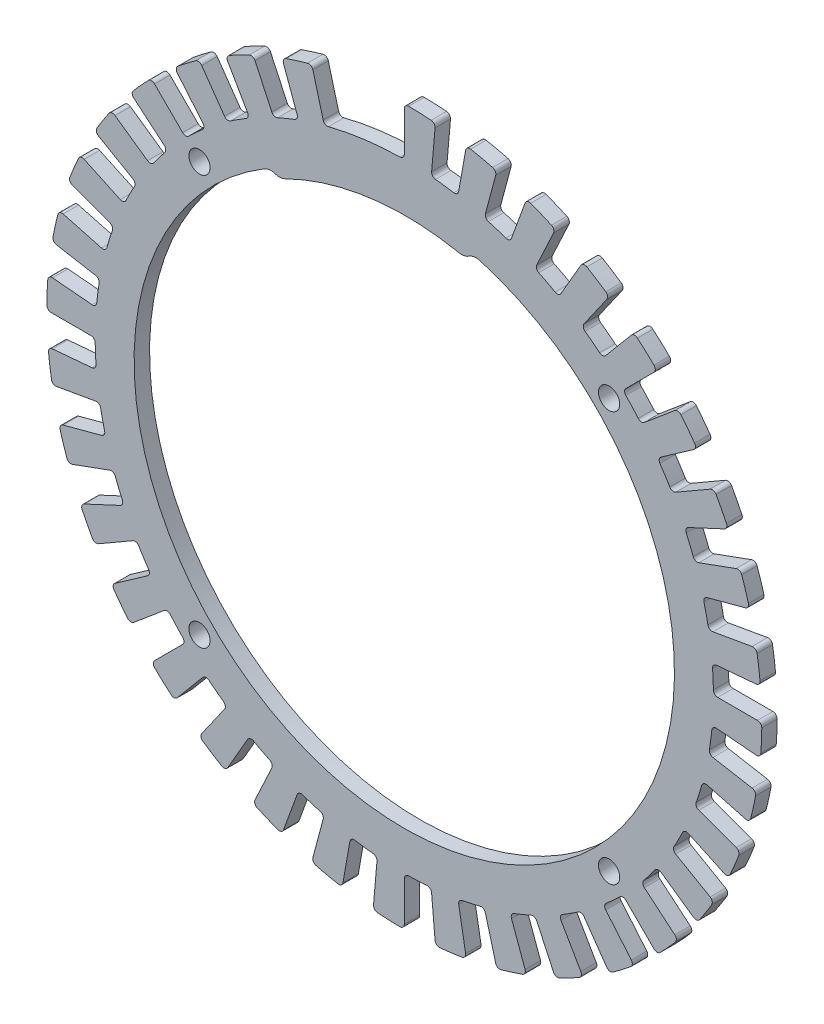
SolidWorks part; units mm, degrees
ref_plane "Front Plane" through (0, 0, 0) normal (0, 0, 1) x (1, 0, 0)
ref_plane "Top Plane" through (0, 0, 0) normal (0, 1, 0) x (1, 0, 0)
ref_plane "Right Plane" through (0, 0, 0) normal (1, 0, 0) x (0, 0, -1)
sketch "Sketch1" plane through (0, 0, 0) normal (0, 0, 1) x (1, 0, 0)
  line L0 (0, 82.7) -> (0, 71.5) construction
  line L1 (7.2078, 82.3853) -> (6.2316, 71.2279) construction
  line L2 (0, 71.5) -> (0, 0) construction
  line L3 (6.2316, 71.2279) -> (0, 0) construction
  line L4 (12.5883, 71.3918) -> (14.186, 80.4528) construction
  line L5 (12.5883, 71.3918) -> (0, 0) construction
  line L8 (0, 0) -> (47.3762, 47.3762) construction
  line L12 (50.5581, 50.5581) -> (47.3762, 47.3762) construction
  line L15 (47.3762, 47.3762) -> (44.1942, 44.1942) construction
  line L18 (7.3144, 72.1301) -> (6.3182, 72.2172) construction
  line L21 (7.3144, 72.1301) -> (7.2135, 71.1352) construction
  line L24 (12.5883, 71.3918) -> (11.6035, 71.5654) construction
  line L27 (11.6035, 71.5654) -> (11.4434, 70.5783) construction
  line L30 (1.0122, 82.6938) -> (1, 81.6939) construction
  line L33 (1, 81.6939) -> (0, 81.6939) construction
  line L36 (7.1201, 81.383) -> (6.1239, 81.4702) construction
  line L39 (6.1239, 81.4702) -> (6.1989, 82.4674) construction
  line L42 (7.1201, 81.383) -> (6.3182, 72.2172)
  line L45 (0, 81.6939) -> (0, 72.4931)
  line L48 (0, 72.4931) -> (-1, 72.4931) construction
  line L51 (-1, 72.4931) -> (-0.9862, 71.4932) construction
  line L109 (0, -82.7) -> (0, -71.5) [skipped]
  line L111 (14.3607, 81.4436) -> (12.4158, 70.4138) [skipped]
  line L115 (41.35, 71.6203) -> (35.75, 61.9208) [skipped]
  line L117 (53.1585, 63.3519) -> (45.9593, 54.7722) [skipped]
  line L118 (-63.3519, -53.1585) -> (-54.7722, -45.9593) [skipped]
  line L119 (63.3519, 53.1585) -> (54.7722, 45.9593) [skipped]
  line L121 (71.6203, 41.35) -> (61.9208, 35.75) [skipped]
  line L123 (77.7126, 28.2851) -> (67.188, 24.4544) [skipped]
  line L125 (81.4436, 14.3607) -> (70.4138, 12.4158) [skipped]
  line L127 (82.7, 0) -> (71.5, 0) [skipped]
  line L129 (81.4436, -14.3607) -> (70.4138, -12.4158) [skipped]
  line L131 (77.7126, -28.2851) -> (67.188, -24.4544) [skipped]
  line L133 (71.6203, -41.35) -> (61.9208, -35.75) [skipped]
  line L135 (63.3519, -53.1585) -> (54.7722, -45.9593) [skipped]
  line L137 (53.1585, -63.3519) -> (45.9593, -54.7722) [skipped]
  line L139 (41.35, -71.6203) -> (35.75, -61.9208) [skipped]
  line L141 (28.2851, -77.7126) -> (24.4544, -67.188) [skipped]
  line L142 (14.3607, -81.4436) -> (12.4158, -70.4138) [skipped]
  line L143 (34.9505, 74.9517) -> (30.2172, 64.801) [skipped]
  line L144 (47.4348, 67.7439) -> (41.0107, 58.5694) [skipped]
  line L145 (58.4777, 58.4777) -> (50.5581, 50.5581) [skipped]
  line L146 (67.7439, 47.4348) -> (58.5694, 41.0107) [skipped]
  line L147 (74.9517, 34.9505) -> (64.801, 30.2172) [skipped]
  line L148 (79.8821, 21.4043) -> (69.0637, 18.5056) [skipped]
  line L149 (82.3853, 7.2078) -> (71.2279, 6.2316) [skipped]
  line L150 (82.3853, -7.2078) -> (71.2279, -6.2316) [skipped]
  line L151 (79.8821, -21.4043) -> (69.0637, -18.5056) [skipped]
  line L152 (74.9517, -34.9505) -> (64.801, -30.2172) [skipped]
  line L153 (67.7439, -47.4348) -> (58.5694, -41.0107) [skipped]
  line L154 (58.4777, -58.4777) -> (50.5581, -50.5581) [skipped]
  line L155 (47.4348, -67.7439) -> (41.0107, -58.5694) [skipped]
  line L156 (34.9505, -74.9517) -> (30.2172, -64.801) [skipped]
  line L157 (21.4043, -79.8821) -> (18.5056, -69.0637) [skipped]
  line L158 (7.2078, -82.3853) -> (6.2316, -71.2279) [skipped]
  line L159 (-7.2078, -82.3853) -> (-6.2316, -71.2279) [skipped]
  line L160 (-21.4043, -79.8821) -> (-18.5056, -69.0637) [skipped]
  line L161 (-34.9505, -74.9517) -> (-30.2172, -64.801) [skipped]
  line L162 (-47.4348, -67.7439) -> (-41.0107, -58.5694) [skipped]
  line L163 (-58.4777, -58.4777) -> (-50.5581, -50.5581) [skipped]
  line L164 (-67.7439, -47.4348) -> (-58.5694, -41.0107) [skipped]
  line L165 (-74.9517, -34.9505) -> (-64.801, -30.2172) [skipped]
  line L166 (-79.8821, -21.4043) -> (-69.0637, -18.5056) [skipped]
  line L167 (-82.3853, -7.2078) -> (-71.2279, -6.2316) [skipped]
  line L168 (-82.3853, 7.2078) -> (-71.2279, 6.2316) [skipped]
  line L169 (-79.8821, 21.4043) -> (-69.0637, 18.5056) [skipped]
  line L170 (-74.9517, 34.9505) -> (-64.801, 30.2172) [skipped]
  line L171 (-67.7439, 47.4348) -> (-58.5694, 41.0107) [skipped]
  line L172 (-58.4777, 58.4777) -> (-50.5581, 50.5581) [skipped]
  line L173 (-47.4348, 67.7439) -> (-41.0107, 58.5694) [skipped]
  line L174 (-34.9505, 74.9517) -> (-30.2172, 64.801) [skipped]
  line L175 (-21.4043, 79.8821) -> (-18.5056, 69.0637) [skipped]
  line L176 (21.4043, 79.8821) -> (18.5056, 69.0637) [skipped]
  line L209 (0, 0) -> (-47.3762, -47.3762) construction
  line L210 (0, 0) -> (-47.3762, 47.3762) construction
  line L211 (0, 0) -> (47.3762, -47.3762) construction
  line L212 (14.186, 80.4528) -> (12.5883, 71.3918)
  line L213 (21.1439, 78.9102) -> (18.7626, 70.023)
  line L214 (27.941, 76.7671) -> (24.7941, 68.1212)
  line L215 (34.5253, 74.0398) -> (30.6369, 65.7011)
  line L216 (40.8469, 70.749) -> (36.2466, 62.7809)
  line L217 (46.8577, 66.9197) -> (41.5803, 59.3829)
  line L218 (52.5118, 62.5811) -> (46.5977, 55.5329)
  line L219 (57.7663, 57.7663) -> (51.2604, 51.2604)
  line L220 (62.5811, 52.5118) -> (55.5329, 46.5977)
  line L221 (66.9197, 46.8577) -> (59.3829, 41.5803)
  line L222 (70.749, 40.8469) -> (62.7809, 36.2466)
  line L223 (74.0398, 34.5253) -> (65.7011, 30.6369)
  line L224 (76.7671, 27.941) -> (68.1212, 24.7941)
  line L225 (78.9102, 21.1439) -> (70.023, 18.7626)
  line L226 (80.4528, 14.186) -> (71.3918, 12.5883)
  line L227 (81.383, 7.1201) -> (72.2172, 6.3182)
  line L228 (81.6939, 0) -> (72.4931, 0)
  line L229 (81.383, -7.1201) -> (72.2172, -6.3182)
  line L230 (80.4528, -14.186) -> (71.3918, -12.5883)
  line L231 (78.9102, -21.1439) -> (70.023, -18.7626)
  line L232 (76.7671, -27.941) -> (68.1212, -24.7941)
  line L233 (74.0398, -34.5253) -> (65.7011, -30.6369)
  line L234 (70.749, -40.8469) -> (62.7809, -36.2466)
  line L235 (66.9197, -46.8577) -> (59.3829, -41.5803)
  line L236 (62.5811, -52.5118) -> (55.5329, -46.5977)
  line L237 (57.7663, -57.7663) -> (51.2604, -51.2604)
  line L238 (52.5118, -62.5811) -> (46.5977, -55.5329)
  line L239 (46.8577, -66.9197) -> (41.5803, -59.3829)
  line L240 (40.8469, -70.749) -> (36.2466, -62.7809)
  line L241 (34.5253, -74.0398) -> (30.6369, -65.7011)
  line L242 (27.941, -76.7671) -> (24.7941, -68.1212)
  line L243 (21.1439, -78.9102) -> (18.7626, -70.023)
  line L244 (14.186, -80.4528) -> (12.5883, -71.3918)
  line L245 (7.1201, -81.383) -> (6.3182, -72.2172)
  line L246 (0, -81.6939) -> (0, -72.4931)
  line L247 (-7.1201, -81.383) -> (-6.3182, -72.2172)
  line L248 (-14.186, -80.4528) -> (-12.5883, -71.3918)
  line L249 (-21.1439, -78.9102) -> (-18.7626, -70.023)
  line L250 (-27.941, -76.7671) -> (-24.7941, -68.1212)
  line L251 (-34.5253, -74.0398) -> (-30.6369, -65.7011)
  line L252 (-40.8469, -70.749) -> (-36.2466, -62.7809)
  line L253 (-46.8577, -66.9197) -> (-41.5803, -59.3829)
  line L254 (-52.5118, -62.5811) -> (-46.5977, -55.5329)
  line L255 (-57.7663, -57.7663) -> (-51.2604, -51.2604)
  line L256 (-62.5811, -52.5118) -> (-55.5329, -46.5977)
  line L257 (-66.9197, -46.8577) -> (-59.3829, -41.5803)
  line L258 (-70.749, -40.8469) -> (-62.7809, -36.2466)
  line L259 (-74.0398, -34.5253) -> (-65.7011, -30.6369)
  line L260 (-76.7671, -27.941) -> (-68.1212, -24.7941)
  line L261 (-78.9102, -21.1439) -> (-70.023, -18.7626)
  line L262 (-80.4528, -14.186) -> (-71.3918, -12.5883)
  line L263 (-81.383, -7.1201) -> (-72.2172, -6.3182)
  line L264 (-81.6939, 0) -> (-72.4931, 0)
  line L265 (-81.383, 7.1201) -> (-72.2172, 6.3182)
  line L266 (-80.4528, 14.186) -> (-71.3918, 12.5883)
  line L267 (-78.9102, 21.1439) -> (-70.023, 18.7626)
  line L268 (-76.7671, 27.941) -> (-68.1212, 24.7941)
  line L269 (-74.0398, 34.5253) -> (-65.7011, 30.6369)
  line L270 (-70.749, 40.8469) -> (-62.7809, 36.2466)
  line L271 (-66.9197, 46.8577) -> (-59.3829, 41.5803)
  line L272 (-62.5811, 52.5118) -> (-55.5329, 46.5977)
  line L273 (-57.7663, 57.7663) -> (-51.2604, 51.2604)
  line L274 (-52.5118, 62.5811) -> (-46.5977, 55.5329)
  line L275 (-46.8577, 66.9197) -> (-41.5803, 59.3829)
  line L276 (-40.8469, 70.749) -> (-36.2466, 62.7809)
  line L277 (-34.5253, 74.0398) -> (-30.6369, 65.7011)
  line L278 (-27.941, 76.7671) -> (-24.7941, 68.1212)
  line L279 (-21.1439, 78.9102) -> (-18.7626, 70.023)
  line L280 (-0.9864, 71.4932) -> (-0.9862, 71.4932)
  line L281 (-32.3995, 53.4464) -> (-30.8444, 50.881) construction
  line L282 (-30.8444, 50.881) -> (-29.8635, 53.7161) construction
  line L283 (-29.8635, 53.7161) -> (-28.8826, 56.5512) construction
  line L284 (-28.8826, 56.5512) -> (-27.5181, 53.8795) construction
  line L285 (17.4626, 60.0109) -> (16.6244, 57.1304) construction
  line L286 (16.6244, 57.1304) -> (14.9432, 59.615) construction
  line L289 (13.262, 62.0997) -> (14.9432, 59.615) construction
  line L290 (-7.4414, 56.5227) -> (0, 0) construction
  line L291 (-27.5181, 53.8795) -> (-7.4414, 56.5227) construction
  line L292 (-7.4414, 56.5227) -> (12.6354, 59.1658) construction
  line L293 (13.262, 62.0997) -> (12.6354, 59.1658) construction
  line L294 (-28.4278, 55.6607) -> (13.0531, 61.1217) construction
  circle A0 centre (0, 0) radius 82.7 construction
  arc A1 (-32.3995, 53.4464) -> (17.4626, 60.0109) centre (0, 0) ccw
  circle A73 centre (47.3762, 47.3762) radius 2.4585
  circle A74 centre (47.3762, 47.3762) radius 2.987 construction
  arc A78 (0, 71.5) -> (6.2316, 71.2279) centre (0, 0) cw construction
  arc A79 (6.3182, 72.2172) -> (7.2135, 71.1352) centre (7.3144, 72.1301) ccw
  arc A80 (11.4434, 70.5783) -> (12.5883, 71.3918) centre (11.6035, 71.5654) ccw construction
  arc A81 (7.1201, 81.383) -> (6.1989, 82.4674) centre (6.1239, 81.4702) ccw
  arc A82 (0, 81.6939) -> (1.0122, 82.6938) centre (1, 81.6939) cw
  arc A83 (6.5367, 74.7146) -> (13.0236, 73.8606) centre (0, 0) cw [skipped]
  arc A84 (7.2135, 71.1352) -> (11.4434, 70.5783) centre (0, 0) cw
  arc A85 (0, 82.7) -> (7.2078, 82.3853) centre (0, 0) cw [skipped]
  arc A86 (1.0122, 82.6938) -> (6.1989, 82.4674) centre (0, 0) cw
  arc A87 (28.2851, 77.7126) -> (34.9505, 74.9517) centre (0, 0) cw [skipped]
  arc A88 (31.6964, 67.9731) -> (37.5, 64.9519) centre (0, 0) cw [skipped]
  arc A89 (41.35, 71.6203) -> (47.4348, 67.7439) centre (0, 0) cw [skipped]
  arc A90 (43.0182, 61.4364) -> (48.2091, 57.4533) centre (0, 0) cw [skipped]
  arc A91 (53.1585, 63.3519) -> (58.4777, 58.4777) centre (0, 0) cw [skipped]
  arc A92 (53.033, 53.033) -> (57.4533, 48.2091) centre (0, 0) cw [skipped]
  arc A93 (63.3519, 53.1585) -> (67.7439, 47.4348) centre (0, 0) cw [skipped]
  arc A94 (61.4364, 43.0182) -> (64.9519, 37.5) centre (0, 0) cw [skipped]
  arc A95 (71.6203, 41.35) -> (74.9517, 34.9505) centre (0, 0) cw [skipped]
  arc A96 (67.9731, 31.6964) -> (70.4769, 25.6515) centre (0, 0) cw [skipped]
  arc A97 (77.7126, 28.2851) -> (79.8821, 21.4043) centre (0, 0) cw [skipped]
  arc A98 (72.4444, 19.4114) -> (73.8606, 13.0236) centre (0, 0) cw [skipped]
  arc A99 (81.4436, 14.3607) -> (82.3853, 7.2078) centre (0, 0) cw [skipped]
  arc A100 (74.7146, 6.5367) -> (75, 0) centre (0, 0) cw [skipped]
  arc A101 (82.7, 0) -> (82.3853, -7.2078) centre (0, 0) cw [skipped]
  arc A102 (74.7146, -6.5367) -> (73.8606, -13.0236) centre (0, 0) cw [skipped]
  arc A103 (81.4436, -14.3607) -> (79.8821, -21.4043) centre (0, 0) cw [skipped]
  arc A104 (72.4444, -19.4114) -> (70.4769, -25.6515) centre (0, 0) cw [skipped]
  arc A105 (77.7126, -28.2851) -> (74.9517, -34.9505) centre (0, 0) cw [skipped]
  arc A106 (67.9731, -31.6964) -> (64.9519, -37.5) centre (0, 0) cw [skipped]
  arc A107 (71.6203, -41.35) -> (67.7439, -47.4348) centre (0, 0) cw [skipped]
  arc A108 (61.4364, -43.0182) -> (57.4533, -48.2091) centre (0, 0) cw [skipped]
  arc A109 (63.3519, -53.1585) -> (58.4777, -58.4777) centre (0, 0) cw [skipped]
  arc A110 (53.033, -53.033) -> (48.2091, -57.4533) centre (0, 0) cw [skipped]
  arc A111 (53.1585, -63.3519) -> (47.4348, -67.7439) centre (0, 0) cw [skipped]
  arc A112 (43.0182, -61.4364) -> (37.5, -64.9519) centre (0, 0) cw [skipped]
  arc A113 (41.35, -71.6203) -> (34.9505, -74.9517) centre (0, 0) cw [skipped]
  arc A114 (31.6964, -67.9731) -> (25.6515, -70.4769) centre (0, 0) cw [skipped]
  arc A115 (28.2851, -77.7126) -> (21.4043, -79.8821) centre (0, 0) cw [skipped]
  arc A116 (19.4114, -72.4444) -> (13.0236, -73.8606) centre (0, 0) cw [skipped]
  arc A117 (14.3607, -81.4436) -> (7.2078, -82.3853) centre (0, 0) cw [skipped]
  arc A118 (6.5367, -74.7146) -> (0, -75) centre (0, 0) cw [skipped]
  arc A119 (0, -82.7) -> (-7.2078, -82.3853) centre (0, 0) cw [skipped]
  arc A120 (-6.5367, -74.7146) -> (-13.0236, -73.8606) centre (0, 0) cw [skipped]
  arc A121 (-14.3607, -81.4436) -> (-21.4043, -79.8821) centre (0, 0) cw [skipped]
  arc A122 (-28.2851, -77.7126) -> (-34.9505, -74.9517) centre (0, 0) cw [skipped]
  arc A123 (-19.4114, -72.4444) -> (-25.6515, -70.4769) centre (0, 0) cw [skipped]
  arc A124 (-31.6964, -67.9731) -> (-37.5, -64.9519) centre (0, 0) cw [skipped]
  arc A125 (-41.35, -71.6203) -> (-47.4348, -67.7439) centre (0, 0) cw [skipped]
  arc A126 (-43.0182, -61.4364) -> (-48.2091, -57.4533) centre (0, 0) cw [skipped]
  arc A127 (-53.1585, -63.3519) -> (-58.4777, -58.4777) centre (0, 0) cw [skipped]
  arc A128 (-53.033, -53.033) -> (-57.4533, -48.2091) centre (0, 0) cw [skipped]
  arc A129 (-63.3519, -53.1585) -> (-67.7439, -47.4348) centre (0, 0) cw [skipped]
  arc A130 (-61.4364, -43.0182) -> (-64.9519, -37.5) centre (0, 0) cw [skipped]
  arc A131 (-71.6203, -41.35) -> (-74.9517, -34.9505) centre (0, 0) cw [skipped]
  arc A132 (-67.9731, -31.6964) -> (-70.4769, -25.6515) centre (0, 0) cw [skipped]
  arc A133 (-77.7126, -28.2851) -> (-79.8821, -21.4043) centre (0, 0) cw [skipped]
  arc A134 (-72.4444, -19.4114) -> (-73.8606, -13.0236) centre (0, 0) cw [skipped]
  arc A135 (-81.4436, -14.3607) -> (-82.3853, -7.2078) centre (0, 0) cw [skipped]
  arc A136 (-74.7146, -6.5367) -> (-75, 0) centre (0, 0) cw [skipped]
  arc A137 (-82.7, 0) -> (-82.3853, 7.2078) centre (0, 0) cw [skipped]
  arc A138 (-74.7146, 6.5367) -> (-73.8606, 13.0236) centre (0, 0) cw [skipped]
  arc A139 (-81.4436, 14.3607) -> (-79.8821, 21.4043) centre (0, 0) cw [skipped]
  arc A140 (-72.4444, 19.4114) -> (-70.4769, 25.6515) centre (0, 0) cw [skipped]
  arc A141 (-77.7126, 28.2851) -> (-74.9517, 34.9505) centre (0, 0) cw [skipped]
  arc A142 (-67.9731, 31.6964) -> (-64.9519, 37.5) centre (0, 0) cw [skipped]
  arc A143 (-71.6203, 41.35) -> (-67.7439, 47.4348) centre (0, 0) cw [skipped]
  arc A144 (-61.4364, 43.0182) -> (-57.4533, 48.2091) centre (0, 0) cw [skipped]
  arc A145 (-63.3519, 53.1585) -> (-58.4777, 58.4777) centre (0, 0) cw [skipped]
  arc A146 (-53.033, 53.033) -> (-48.2091, 57.4533) centre (0, 0) cw [skipped]
  arc A147 (-53.1585, 63.3519) -> (-47.4348, 67.7439) centre (0, 0) cw [skipped]
  arc A148 (-43.0182, 61.4364) -> (-37.5, 64.9519) centre (0, 0) cw [skipped]
  arc A149 (-41.35, 71.6203) -> (-34.9505, 74.9517) centre (0, 0) cw [skipped]
  arc A150 (-31.6964, 67.9731) -> (-25.6515, 70.4769) centre (0, 0) cw [skipped]
  arc A151 (-28.2851, 77.7126) -> (-21.4043, 79.8821) centre (0, 0) cw [skipped]
  arc A152 (-19.4114, 72.4444) -> (-13.0236, 73.8606) centre (0, 0) cw [skipped]
  arc A153 (14.3607, 81.4436) -> (21.4043, 79.8821) centre (0, 0) cw [skipped]
  arc A154 (19.4114, 72.4444) -> (25.6515, 70.4769) centre (0, 0) cw [skipped]
  arc A155 (0, 72.4931) -> (-0.9862, 71.4932) centre (-1, 72.4931) cw
  circle A367 centre (-47.3762, -47.3762) radius 2.4585
  circle A368 centre (47.3762, -47.3762) radius 2.4585
  circle A369 centre (-47.3762, 47.3762) radius 2.4585
  circle A370 centre (0, 0) radius 71.5 construction
  arc A371 (12.5883, 71.3918) -> (11.4434, 70.5783) centre (11.6035, 71.5654) cw
  arc A372 (14.186, 80.4528) -> (15.3565, 81.2617) centre (15.1708, 80.2791) cw
  arc A373 (15.3565, 81.2617) -> (20.425, 80.1381) centre (0, 0) cw
  arc A374 (21.1439, 78.9102) -> (20.425, 80.1381) centre (20.178, 79.169) ccw
  arc A375 (18.7626, 70.023) -> (19.4564, 68.8019) centre (19.7285, 69.7641) ccw
  arc A376 (19.4564, 68.8019) -> (23.5254, 67.5189) centre (0, 0) cw
  arc A377 (24.7941, 68.1212) -> (23.5254, 67.5189) centre (23.8544, 68.4633) cw
  arc A378 (27.941, 76.7671) -> (29.2341, 77.3606) centre (28.8806, 76.4251) cw
  arc A379 (29.2341, 77.3606) -> (34.0305, 75.3738) centre (0, 0) cw
  arc A380 (34.5253, 74.0398) -> (34.0305, 75.3738) centre (33.619, 74.4624) ccw
  arc A381 (30.6369, 65.7011) -> (31.1081, 64.3781) centre (31.5432, 65.2784) ccw
  arc A382 (31.1081, 64.3781) -> (34.8925, 62.408) centre (0, 0) cw
  arc A384 (36.2466, 62.7809) -> (34.8925, 62.408) centre (35.3805, 63.2809) cw
  arc A385 (40.8469, 70.749) -> (42.2235, 71.1088) centre (41.713, 70.249) cw
  arc A386 (42.2235, 71.1088) -> (46.602, 68.3194) centre (0, 0) cw
  arc A387 (46.8577, 66.9197) -> (46.602, 68.3194) centre (46.0385, 67.4933) ccw
  arc A388 (41.5803, 59.3829) -> (41.8147, 57.9981) centre (42.3995, 58.8093) ccw
  arc A389 (41.8147, 57.9981) -> (45.1995, 55.4009) centre (0, 0) cw
  arc A390 (46.5977, 55.5329) -> (45.1995, 55.4009) centre (45.8316, 56.1757) cw
  arc A391 (52.5118, 62.5811) -> (53.93, 62.6965) centre (53.2779, 61.9384) cw
  arc A392 (53.93, 62.6965) -> (57.7576, 59.1891) centre (0, 0) cw
  arc A393 (57.7663, 57.7663) -> (57.7576, 59.1891) centre (57.0592, 58.4734) ccw
  arc A394 (51.2604, 51.2604) -> (51.2507, 49.856) centre (51.9675, 50.5533) ccw
  arc A395 (51.2507, 49.856) -> (54.133, 46.7104) centre (0, 0) cw
  arc A396 (55.5329, 46.5977) -> (54.133, 46.7104) centre (54.8902, 47.3637) cw
  arc A397 (62.5811, 52.5118) -> (63.9978, 52.3791) centre (63.2239, 51.7458) cw
  arc A398 (63.9978, 52.3791) -> (67.1582, 48.2604) centre (0, 0) cw
  arc A399 (66.9197, 46.8577) -> (67.1582, 48.2604) centre (66.3461, 47.6768) ccw
  arc A400 (59.3829, 41.5803) -> (59.1295, 40.199) centre (59.9565, 40.7612) ccw
  arc A401 (59.1295, 40.199) -> (61.4218, 36.6007) centre (0, 0) cw
  arc A402 (62.7809, 36.2466) -> (61.4218, 36.6007) centre (62.2809, 37.1126) cw
  arc A403 (70.749, 40.8469) -> (72.1211, 40.4703) centre (71.249, 39.9809) cw
  arc A404 (72.1211, 40.4703) -> (74.5182, 35.8653) centre (0, 0) cw
  arc A405 (74.0398, 34.5253) -> (74.5182, 35.8653) centre (73.6172, 35.4316) ccw
  arc A406 (65.7011, 30.6369) -> (65.2116, 29.3205) centre (66.1237, 29.7306) ccw
  arc A407 (65.2116, 29.3205) -> (66.8443, 25.3788) centre (0, 0) cw
  arc A408 (68.1212, 24.7941) -> (66.8443, 25.3788) centre (67.7792, 25.7338) cw
  arc A409 (76.7671, 27.941) -> (78.053, 27.3318) centre (77.1092, 27.0013) cw
  arc A410 (78.053, 27.3318) -> (79.6141, 22.3805) centre (0, 0) cw
  arc A411 (78.9102, 21.1439) -> (79.6141, 22.3805) centre (78.6514, 22.1099) ccw
  arc A412 (70.023, 18.7626) -> (69.3124, 17.5512) centre (70.2818, 17.7967) ccw
  arc A413 (69.3124, 17.5512) -> (70.2358, 13.3859) centre (0, 0) cw
  arc A414 (71.3918, 12.5883) -> (70.2358, 13.3859) centre (71.2181, 13.5731) cw
  arc A415 (80.4528, 14.186) -> (81.6133, 13.3628) centre (80.6264, 13.2012) cw
  arc A416 (81.6133, 13.3628) -> (82.2909, 8.2156) centre (0, 0) cw
  arc A417 (81.383, 7.1201) -> (82.2909, 8.2156) centre (81.2959, 8.1163) ccw
  arc A418 (72.2172, 6.3182) -> (71.3071, 5.2486) centre (72.3044, 5.322) ccw
  arc A419 (71.3071, 5.2486) -> (71.4932, 0.9862) centre (0, 0) cw
  arc A420 (72.4931, 0) -> (71.4932, 0.9862) centre (72.4931, 1) cw
  arc A421 (81.6939, 0) -> (82.6938, -1.0122) centre (81.6939, -1) cw
  arc A422 (82.6938, -1.0122) -> (82.4674, -6.1989) centre (0, 0) cw
  arc A423 (81.383, -7.1201) -> (82.4674, -6.1989) centre (81.4702, -6.1239) ccw
  arc A424 (72.2172, -6.3182) -> (71.1352, -7.2135) centre (72.1301, -7.3144) ccw
  arc A425 (71.1352, -7.2135) -> (70.5783, -11.4434) centre (0, 0) cw
  arc A426 (71.3918, -12.5883) -> (70.5783, -11.4434) centre (71.5654, -11.6035) cw
  arc A427 (80.4528, -14.186) -> (81.2617, -15.3565) centre (80.2791, -15.1708) cw
  arc A428 (81.2617, -15.3565) -> (80.1381, -20.425) centre (0, 0) cw
  arc A429 (78.9102, -21.1439) -> (80.1381, -20.425) centre (79.169, -20.178) ccw
  arc A430 (70.023, -18.7626) -> (68.8019, -19.4564) centre (69.7641, -19.7285) ccw
  arc A431 (68.8019, -19.4564) -> (67.5189, -23.5254) centre (0, 0) cw
  arc A432 (68.1212, -24.7941) -> (67.5189, -23.5254) centre (68.4633, -23.8544) cw
  arc A433 (76.7671, -27.941) -> (77.3606, -29.2341) centre (76.4251, -28.8806) cw
  arc A434 (77.3606, -29.2341) -> (75.3738, -34.0305) centre (0, 0) cw
  arc A435 (74.0398, -34.5253) -> (75.3738, -34.0305) centre (74.4624, -33.619) ccw
  arc A436 (65.7011, -30.6369) -> (64.3781, -31.1081) centre (65.2784, -31.5432) ccw
  arc A437 (64.3781, -31.1081) -> (62.408, -34.8925) centre (0, 0) cw
  arc A438 (62.7809, -36.2466) -> (62.408, -34.8925) centre (63.2809, -35.3805) cw
  arc A439 (70.749, -40.8469) -> (71.1088, -42.2235) centre (70.249, -41.713) cw
  arc A440 (71.1088, -42.2235) -> (68.3194, -46.602) centre (0, 0) cw
  arc A441 (66.9197, -46.8577) -> (68.3194, -46.602) centre (67.4933, -46.0385) ccw
  arc A442 (59.3829, -41.5803) -> (57.9981, -41.8147) centre (58.8093, -42.3995) ccw
  arc A443 (57.9981, -41.8147) -> (55.4009, -45.1995) centre (0, 0) cw
  arc A444 (55.5329, -46.5977) -> (55.4009, -45.1995) centre (56.1757, -45.8316) cw
  arc A445 (62.5811, -52.5118) -> (62.6965, -53.93) centre (61.9384, -53.2779) cw
  arc A446 (62.6965, -53.93) -> (59.1891, -57.7576) centre (0, 0) cw
  arc A447 (57.7663, -57.7663) -> (59.1891, -57.7576) centre (58.4734, -57.0592) ccw
  arc A448 (51.2604, -51.2604) -> (49.856, -51.2507) centre (50.5533, -51.9675) ccw
  arc A449 (49.856, -51.2507) -> (46.7104, -54.133) centre (0, 0) cw
  arc A450 (46.5977, -55.5329) -> (46.7104, -54.133) centre (47.3637, -54.8902) cw
  arc A451 (52.5118, -62.5811) -> (52.3791, -63.9978) centre (51.7458, -63.2239) cw
  arc A452 (52.3791, -63.9978) -> (48.2604, -67.1582) centre (0, 0) cw
  arc A453 (46.8577, -66.9197) -> (48.2604, -67.1582) centre (47.6768, -66.3461) ccw
  arc A454 (41.5803, -59.3829) -> (40.199, -59.1295) centre (40.7612, -59.9565) ccw
  arc A455 (40.199, -59.1295) -> (36.6007, -61.4218) centre (0, 0) cw
  arc A456 (36.2466, -62.7809) -> (36.6007, -61.4218) centre (37.1126, -62.2809) cw
  arc A457 (40.8469, -70.749) -> (40.4703, -72.1211) centre (39.9809, -71.249) cw
  arc A458 (40.4703, -72.1211) -> (35.8653, -74.5182) centre (0, 0) cw
  arc A459 (34.5253, -74.0398) -> (35.8653, -74.5182) centre (35.4316, -73.6172) ccw
  arc A460 (30.6369, -65.7011) -> (29.3205, -65.2116) centre (29.7306, -66.1237) ccw
  arc A461 (29.3205, -65.2116) -> (25.3788, -66.8443) centre (0, 0) cw
  arc A462 (24.7941, -68.1212) -> (25.3788, -66.8443) centre (25.7338, -67.7792) cw
  arc A463 (27.941, -76.7671) -> (27.3318, -78.053) centre (27.0013, -77.1092) cw
  arc A464 (27.3318, -78.053) -> (22.3805, -79.6141) centre (0, 0) cw
  arc A465 (21.1439, -78.9102) -> (22.3805, -79.6141) centre (22.1099, -78.6514) ccw
  arc A466 (18.7626, -70.023) -> (17.5512, -69.3124) centre (17.7967, -70.2818) ccw
  arc A467 (17.5512, -69.3124) -> (13.3859, -70.2358) centre (0, 0) cw
  arc A468 (12.5883, -71.3918) -> (13.3859, -70.2358) centre (13.5731, -71.2181) cw
  arc A469 (14.186, -80.4528) -> (13.3628, -81.6133) centre (13.2012, -80.6264) cw
  arc A470 (13.3628, -81.6133) -> (8.2156, -82.2909) centre (0, 0) cw
  arc A471 (7.1201, -81.383) -> (8.2156, -82.2909) centre (8.1163, -81.2959) ccw
  arc A472 (6.3182, -72.2172) -> (5.2486, -71.3071) centre (5.322, -72.3044) ccw
  arc A473 (5.2486, -71.3071) -> (0.9862, -71.4932) centre (0, 0) cw
  arc A474 (0, -72.4931) -> (0.9862, -71.4932) centre (1, -72.4931) cw
  arc A475 (0, -81.6939) -> (-1.0122, -82.6938) centre (-1, -81.6939) cw
  arc A476 (-1.0122, -82.6938) -> (-6.1989, -82.4674) centre (0, 0) cw
  arc A477 (-7.1201, -81.383) -> (-6.1989, -82.4674) centre (-6.1239, -81.4702) ccw
  arc A478 (-6.3182, -72.2172) -> (-7.2135, -71.1352) centre (-7.3144, -72.1301) ccw
  arc A479 (-7.2135, -71.1352) -> (-11.4434, -70.5783) centre (0, 0) cw
  arc A480 (-12.5883, -71.3918) -> (-11.4434, -70.5783) centre (-11.6035, -71.5654) cw
  arc A481 (-14.186, -80.4528) -> (-15.3565, -81.2617) centre (-15.1708, -80.2791) cw
  arc A482 (-15.3565, -81.2617) -> (-20.425, -80.1381) centre (0, 0) cw
  arc A483 (-21.1439, -78.9102) -> (-20.425, -80.1381) centre (-20.178, -79.169) ccw
  arc A484 (-18.7626, -70.023) -> (-19.4564, -68.8019) centre (-19.7285, -69.7641) ccw
  arc A485 (-19.4564, -68.8019) -> (-23.5254, -67.5189) centre (0, 0) cw
  arc A486 (-24.7941, -68.1212) -> (-23.5254, -67.5189) centre (-23.8544, -68.4633) cw
  arc A487 (-27.941, -76.7671) -> (-29.2341, -77.3606) centre (-28.8806, -76.4251) cw
  arc A488 (-29.2341, -77.3606) -> (-34.0305, -75.3738) centre (0, 0) cw
  arc A489 (-34.5253, -74.0398) -> (-34.0305, -75.3738) centre (-33.619, -74.4624) ccw
  arc A490 (-30.6369, -65.7011) -> (-31.1081, -64.3781) centre (-31.5432, -65.2784) ccw
  arc A491 (-31.1081, -64.3781) -> (-34.8925, -62.408) centre (0, 0) cw
  arc A492 (-36.2466, -62.7809) -> (-34.8925, -62.408) centre (-35.3805, -63.2809) cw
  arc A493 (-40.8469, -70.749) -> (-42.2235, -71.1088) centre (-41.713, -70.249) cw
  arc A494 (-42.2235, -71.1088) -> (-46.602, -68.3194) centre (0, 0) cw
  arc A495 (-46.8577, -66.9197) -> (-46.602, -68.3194) centre (-46.0385, -67.4933) ccw
  arc A496 (-41.5803, -59.3829) -> (-41.8147, -57.9981) centre (-42.3995, -58.8093) ccw
  arc A497 (-41.8147, -57.9981) -> (-45.1995, -55.4009) centre (0, 0) cw
  arc A498 (-46.5977, -55.5329) -> (-45.1995, -55.4009) centre (-45.8316, -56.1757) cw
  arc A499 (-52.5118, -62.5811) -> (-53.93, -62.6965) centre (-53.2779, -61.9384) cw
  arc A500 (-53.93, -62.6965) -> (-57.7576, -59.1891) centre (0, 0) cw
  arc A501 (-57.7663, -57.7663) -> (-57.7576, -59.1891) centre (-57.0592, -58.4734) ccw
  arc A502 (-51.2604, -51.2604) -> (-51.2507, -49.856) centre (-51.9675, -50.5533) ccw
  arc A503 (-51.2507, -49.856) -> (-54.133, -46.7104) centre (0, 0) cw
  arc A504 (-55.5329, -46.5977) -> (-54.133, -46.7104) centre (-54.8902, -47.3637) cw
  arc A505 (-62.5811, -52.5118) -> (-63.9978, -52.3791) centre (-63.2239, -51.7458) cw
  arc A506 (-63.9978, -52.3791) -> (-67.1582, -48.2604) centre (0, 0) cw
  arc A507 (-66.9197, -46.8577) -> (-67.1582, -48.2604) centre (-66.3461, -47.6768) ccw
  arc A508 (-59.3829, -41.5803) -> (-59.1295, -40.199) centre (-59.9565, -40.7612) ccw
  arc A509 (-59.1295, -40.199) -> (-61.4218, -36.6007) centre (0, 0) cw
  arc A510 (-62.7809, -36.2466) -> (-61.4218, -36.6007) centre (-62.2809, -37.1126) cw
  arc A511 (-70.749, -40.8469) -> (-72.1211, -40.4703) centre (-71.249, -39.9809) cw
  arc A512 (-72.1211, -40.4703) -> (-74.5182, -35.8653) centre (0, 0) cw
  arc A513 (-74.0398, -34.5253) -> (-74.5182, -35.8653) centre (-73.6172, -35.4316) ccw
  arc A514 (-65.7011, -30.6369) -> (-65.2116, -29.3205) centre (-66.1237, -29.7306) ccw
  arc A515 (-65.2116, -29.3205) -> (-66.8443, -25.3788) centre (0, 0) cw
  arc A516 (-68.1212, -24.7941) -> (-66.8443, -25.3788) centre (-67.7792, -25.7338) cw
  arc A517 (-76.7671, -27.941) -> (-78.053, -27.3318) centre (-77.1092, -27.0013) cw
  arc A518 (-78.053, -27.3318) -> (-79.6141, -22.3805) centre (0, 0) cw
  arc A519 (-78.9102, -21.1439) -> (-79.6141, -22.3805) centre (-78.6514, -22.1099) ccw
  arc A520 (-70.023, -18.7626) -> (-69.3124, -17.5512) centre (-70.2818, -17.7967) ccw
  arc A521 (-69.3124, -17.5512) -> (-70.2358, -13.3859) centre (0, 0) cw
  arc A522 (-71.3918, -12.5883) -> (-70.2358, -13.3859) centre (-71.2181, -13.5731) cw
  arc A523 (-80.4528, -14.186) -> (-81.6133, -13.3628) centre (-80.6264, -13.2012) cw
  arc A524 (-81.6133, -13.3628) -> (-82.2909, -8.2156) centre (0, 0) cw
  arc A525 (-81.383, -7.1201) -> (-82.2909, -8.2156) centre (-81.2959, -8.1163) ccw
  arc A526 (-72.2172, -6.3182) -> (-71.3071, -5.2486) centre (-72.3044, -5.322) ccw
  arc A527 (-71.3071, -5.2486) -> (-71.4932, -0.9862) centre (0, 0) cw
  arc A528 (-72.4931, 0) -> (-71.4932, -0.9862) centre (-72.4931, -1) cw
  arc A529 (-81.6939, 0) -> (-82.6938, 1.0122) centre (-81.6939, 1) cw
  arc A530 (-82.6938, 1.0122) -> (-82.4674, 6.1989) centre (0, 0) cw
  arc A531 (-81.383, 7.1201) -> (-82.4674, 6.1989) centre (-81.4702, 6.1239) ccw
  arc A532 (-72.2172, 6.3182) -> (-71.1352, 7.2135) centre (-72.1301, 7.3144) ccw
  arc A533 (-71.1352, 7.2135) -> (-70.5783, 11.4434) centre (0, 0) cw
  arc A534 (-71.3918, 12.5883) -> (-70.5783, 11.4434) centre (-71.5654, 11.6035) cw
  arc A535 (-80.4528, 14.186) -> (-81.2617, 15.3565) centre (-80.2791, 15.1708) cw
  arc A536 (-81.2617, 15.3565) -> (-80.1381, 20.425) centre (0, 0) cw
  arc A537 (-78.9102, 21.1439) -> (-80.1381, 20.425) centre (-79.169, 20.178) ccw
  arc A538 (-70.023, 18.7626) -> (-68.8019, 19.4564) centre (-69.7641, 19.7285) ccw
  arc A539 (-68.8019, 19.4564) -> (-67.5189, 23.5254) centre (0, 0) cw
  arc A540 (-68.1212, 24.7941) -> (-67.5189, 23.5254) centre (-68.4633, 23.8544) cw
  arc A541 (-76.7671, 27.941) -> (-77.3606, 29.2341) centre (-76.4251, 28.8806) cw
  arc A542 (-77.3606, 29.2341) -> (-75.3738, 34.0305) centre (0, 0) cw
  arc A543 (-74.0398, 34.5253) -> (-75.3738, 34.0305) centre (-74.4624, 33.619) ccw
  arc A544 (-65.7011, 30.6369) -> (-64.3781, 31.1081) centre (-65.2784, 31.5432) ccw
  arc A545 (-64.3781, 31.1081) -> (-62.408, 34.8925) centre (0, 0) cw
  arc A546 (-62.7809, 36.2466) -> (-62.408, 34.8925) centre (-63.2809, 35.3805) cw
  arc A547 (-70.749, 40.8469) -> (-71.1088, 42.2235) centre (-70.249, 41.713) cw
  arc A548 (-71.1088, 42.2235) -> (-68.3194, 46.602) centre (0, 0) cw
  arc A549 (-66.9197, 46.8577) -> (-68.3194, 46.602) centre (-67.4933, 46.0385) ccw
  arc A550 (-59.3829, 41.5803) -> (-57.9981, 41.8147) centre (-58.8093, 42.3995) ccw
  arc A551 (-57.9981, 41.8147) -> (-55.4009, 45.1995) centre (0, 0) cw
  arc A552 (-55.5329, 46.5977) -> (-55.4009, 45.1995) centre (-56.1757, 45.8316) cw
  arc A553 (-62.5811, 52.5118) -> (-62.6965, 53.93) centre (-61.9384, 53.2779) cw
  arc A554 (-62.6965, 53.93) -> (-59.1891, 57.7576) centre (0, 0) cw
  arc A555 (-57.7663, 57.7663) -> (-59.1891, 57.7576) centre (-58.4734, 57.0592) ccw
  arc A556 (-51.2604, 51.2604) -> (-49.856, 51.2507) centre (-50.5533, 51.9675) ccw
  arc A557 (-49.856, 51.2507) -> (-46.7104, 54.133) centre (0, 0) cw
  arc A558 (-46.5977, 55.5329) -> (-46.7104, 54.133) centre (-47.3637, 54.8902) cw
  arc A559 (-52.5118, 62.5811) -> (-52.3791, 63.9978) centre (-51.7458, 63.2239) cw
  arc A560 (-52.3791, 63.9978) -> (-48.2604, 67.1582) centre (0, 0) cw
  arc A561 (-46.8577, 66.9197) -> (-48.2604, 67.1582) centre (-47.6768, 66.3461) ccw
  arc A562 (-41.5803, 59.3829) -> (-40.199, 59.1295) centre (-40.7612, 59.9565) ccw
  arc A563 (-40.199, 59.1295) -> (-36.6007, 61.4218) centre (0, 0) cw
  arc A564 (-36.2466, 62.7809) -> (-36.6007, 61.4218) centre (-37.1126, 62.2809) cw
  arc A565 (-40.8469, 70.749) -> (-40.4703, 72.1211) centre (-39.9809, 71.249) cw
  arc A566 (-40.4703, 72.1211) -> (-35.8653, 74.5182) centre (0, 0) cw
  arc A567 (-34.5253, 74.0398) -> (-35.8653, 74.5182) centre (-35.4316, 73.6172) ccw
  arc A568 (-30.6369, 65.7011) -> (-29.3205, 65.2116) centre (-29.7306, 66.1237) ccw
  arc A569 (-29.3205, 65.2116) -> (-25.3788, 66.8443) centre (0, 0) cw
  arc A570 (-24.7941, 68.1212) -> (-25.3788, 66.8443) centre (-25.7338, 67.7792) cw
  arc A571 (-27.941, 76.7671) -> (-27.3318, 78.053) centre (-27.0013, 77.1092) cw
  arc A572 (-27.3318, 78.053) -> (-22.3805, 79.6141) centre (0, 0) cw
  arc A573 (-21.1439, 78.9102) -> (-22.3805, 79.6141) centre (-22.1099, 78.6514) ccw
  arc A574 (-18.7626, 70.023) -> (-17.5512, 69.3124) centre (-17.7967, 70.2818) ccw
  arc A575 (-17.5512, 69.3124) -> (-13.3859, 70.2358) centre (0, 0) cw
  arc A576 (-13.3859, 70.2358) -> (-0.9864, 71.4932) centre (0, 0) cw
  arc A577 (-29.8635, 53.7161) -> (-32.3995, 53.4464) centre (-30.8444, 50.881) ccw
  arc A578 (-29.8635, 53.7161) -> (-27.5181, 53.8795) centre (-28.8826, 56.5512) ccw
  arc A579 (17.4626, 60.0109) -> (14.9432, 59.615) centre (16.6244, 57.1304) ccw
  arc A580 (14.9432, 59.615) -> (12.6354, 59.1658) centre (13.262, 62.0997) cw
  circle A582 centre (0, 0) radius 62.5 construction
  arc A586 (-27.5181, 53.8795) -> (12.6354, 59.1658) centre (0.3099, -2.3542) cw
  point P3 (-28.4278, 55.6607)
  point P29 (0, 0)
  point P133 (13.0531, 61.1217)
  point P252 (0, 0)
  point P728 (0, 0)
  point P763 (0, 0)
  dimension "D2" = 165.4
  dimension "D7" = 4.917
  dimension "D8" = 5.974
  dimension "D12" = 1
  dimension "D14" = 11.2
  dimension "D15" = 11.2
  dimension "D17" = 2
  dimension "D3" = 5
  dimension "D4" = 67
  dimension "D6" = 45
  dimension "D10" = 67
  dimension "D11" = 5
  dimension "D9" = 4.5
  dimension "D16" = 7.5
  dimension "D18" = 40.5
  dimension "D19" = 3
  dimension "D5" = 35
  dimension "D13" = 35
extrude "Boss-Extrude1" add sketch "Sketch1" along normal blind 3.5719
